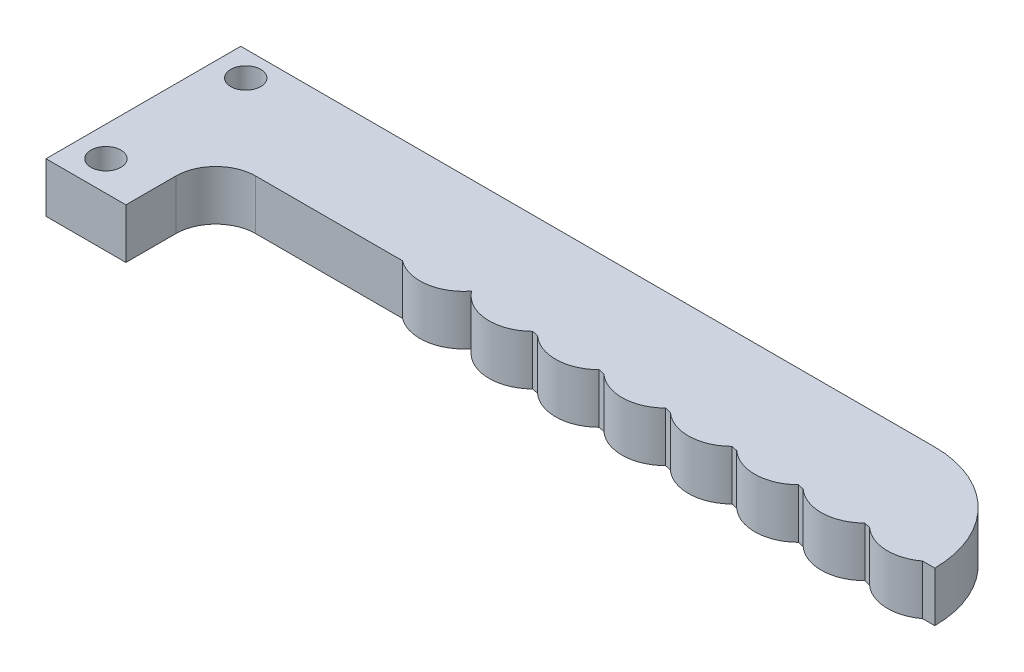
SolidWorks part; units mm, degrees
ref_plane "Front Plane" through (0, 0, 0) normal (0, 0, 1) x (1, 0, 0)
ref_plane "Top Plane" through (0, 0, 0) normal (0, 1, 0) x (1, 0, 0)
ref_plane "Right Plane" through (0, 0, 0) normal (1, 0, 0) x (0, 0, -1)
ref_plane "Plane1" through (0, 0, 0) normal (0, -1, 0) x (1, 0, 0)
sketch "Sketch1" plane through (0, 0, 0) normal (0, -1, 0) x (1, 0, 0)
  line L0 (31.15, -4.375) -> (-45, -4.375) construction
  line L1 (-45, -0.875) -> (-45, -11.375)
  line L2 (-45, -11.375) -> (24.5, -11.375)
  line L3 (35, -0.875) -> (33.775, -0.875)
  line L4 (-45, -0.875) -> (-18.306, -0.875)
  arc A0 (24.5, -11.375) -> (35, -0.875) centre (24.5, -0.875) ccw
  arc A1 (33.775, -0.875) -> (27.825, -1.5316) centre (31.15, -4.375) ccw
  arc A2 (27.825, -1.5316) -> (21.175, -1.5316) centre (24.5, -4.375) ccw
  arc A3 (21.175, -1.5316) -> (14.525, -1.5316) centre (17.85, -4.375) ccw
  arc A4 (14.525, -1.5316) -> (7.875, -1.5316) centre (11.2, -4.375) ccw
  arc A5 (7.875, -1.5316) -> (1.225, -1.5316) centre (4.55, -4.375) ccw
  arc A6 (1.225, -1.5316) -> (-5.425, -1.5316) centre (-2.1, -4.375) ccw
  arc A7 (-5.425, -1.5316) -> (-12.2155, -1.7046) centre (-8.75, -4.375) ccw
  circle A8 centre (17.85, 59.7613) radius 60 construction
  arc A9 (-12.2155, -1.7046) -> (-18.306, -0.875) centre (-15.681, -4.375) ccw
  dimension "D2" = 120
  dimension "D3" = 4.375
  dimension "D4" = 4.375
  dimension "D5" = 4.375
  dimension "D6" = 4.375
  dimension "D7" = 4.375
  dimension "D8" = 4.375
  dimension "D9" = 4.375
  dimension "D10" = 4.375
  dimension "D1" = 80
  dimension "D11" = 10.5
extrude "Boss-Extrude1" add sketch "Sketch1" against normal blind 5
sketch "Sketch2" plane through (0, 0, -0.875) normal (0, 0, 1) x (1, 0, 0)
  line L0 (-37, 5) -> (-37, 0)
  line L1 (-37, 0) -> (-45, 0)
  line L2 (-45, 0) -> (-45, 5)
  line L3 (-45, 5) -> (-37, 5)
  line L9 (-45, 5) -> (-45, 0) construction
  line L10 (-18.306, 0) -> (-45, 0) construction
  line L11 (-18.306, 5) -> (-45, 5) construction
  dimension "D1" = 8
extrude "Boss-Extrude2" add sketch "Sketch2" along normal blind 9
chamfer "Chamfer1" distance 0.5 angle 36.87 6 edges at (21.175, 2.5, -1.5316) (1.225, 2.5, -1.5316) (27.825, 2.5, -1.5316) (7.875, 2.5, -1.5316) (-5.425, 2.5, -1.5316) (14.525, 2.5, -1.5316) first distance on face at (24.5, 2.5, -0.7658) first distance on face at (4.55, 2.5, -0.7658) first distance on face at (30.7351, 2.5, -0.6148) first distance on face at (11.2, 2.5, -0.7658) first distance on face at (-2.1, 2.5, -0.7658) first distance on face at (17.85, 2.5, -0.7658)
fillet "Fillet1" radius 4 1 edges at (-37, 2.5, -0.875) tangent propagation no
sketch "Sketch3" plane through (0, 5, 0) normal (0, 1, 0) x (1, 0, 0)
  line L0 (-42, 11.375) -> (-42, -8.125) construction
  line L1 (-45, 11.375) -> (24.5, 11.375) construction
  line L2 (-37, -8.125) -> (-45, -8.125) construction
  line L4 (-45, -8.125) -> (-45, 11.375) construction
  circle A0 centre (-42, -5.125) radius 1.5
  circle A1 centre (-42, 8.875) radius 1.5
  point P6 (-42, 9.6058)
  dimension "D5" = 3
  dimension "D1" = 3
  dimension "D2" = 14
  dimension "D3" = 2.5
extrude "Cut-Extrude1" cut sketch "Sketch3" against normal blind 10
